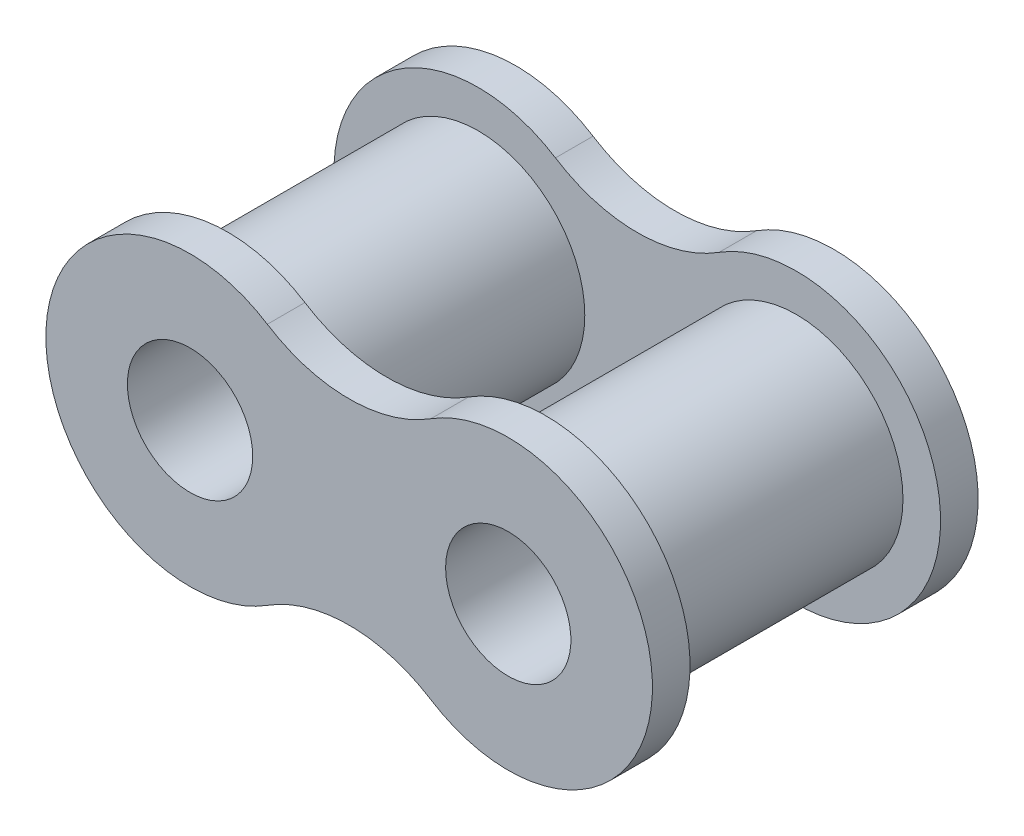
SolidWorks part; units mm, degrees
ref_plane "Front Plane" through (0, 0, 0) normal (0, 0, 1) x (1, 0, 0)
ref_plane "Top Plane" through (0, 0, 0) normal (0, 1, 0) x (1, 0, 0)
ref_plane "Right Plane" through (0, 0, 0) normal (1, 0, 0) x (0, 0, -1)
sketch "Sketch1" plane through (0, 0, 0) normal (0, 0, 1) x (1, 0, 0)
  line L0 (0, 0) -> (-6.35, 0) construction
  line L1 (0, 0) -> (0, 10) construction
  circle A0 centre (-6.35, 0) radius 4.255
  circle A1 centre (6.35, 0) radius 4.255
  arc A2 (-3.265, 4.8583) -> (-3.265, -4.8583) centre (-6.35, 0) ccw
  arc A3 (3.265, 4.8583) -> (3.265, -4.8583) centre (6.35, 0) cw
  arc A4 (-3.265, 4.8583) -> (3.265, 4.8583) centre (0, 10) ccw
  arc A5 (-3.265, -4.8583) -> (3.265, -4.8583) centre (0, -10) cw
  circle A6 centre (-6.35, 0) radius 5.755 construction
  dimension "D2" = 8.51
  dimension "D1" = 12.7
  dimension "D4" = 10
  dimension "D3" = 1.5
extrude "Boss-Extrude3" add sketch "Sketch1" along normal mid plane 10 contours A1 | A0 region at (6.35, 0, 0)
extrude "Boss-Extrude7" add sketch "Sketch1<5>" against normal blind 1.5 from offset 5 contours A2 A5 A3 A4 offset against normal yes
sketch "Sketch1<5>" plane through (0, 0, 0) normal (0, 0, 1) x (1, 0, 0) same geometry as "Sketch1"
mirror "Mirror1" about plane through (0, 0, 0) normal (0, 0, 1) of "Boss-Extrude7"
sketch "Sketch2" plane through (0, 0, 0) normal (0, 0, 1) x (1, 0, 0)
  line L0 (0, 0) -> (0, 3.9092) construction
  circle A0 centre (-6.35, 0) radius 2.5
  arc A1 (-3.265, 4.8583) -> (3.265, 4.8583) centre (0, 10) ccw construction
  circle A2 centre (6.35, 0) radius 2.5
  dimension "D1" = 5
extrude "Cut-Extrude1" cut sketch "Sketch2" against normal through all both and the other way through all
